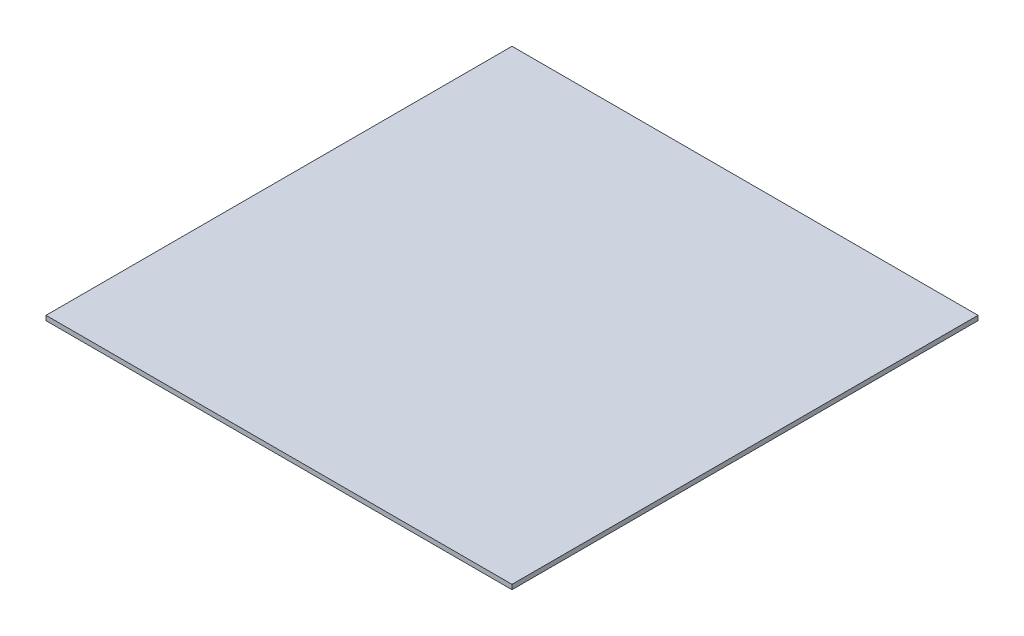
SolidWorks part; units mm, degrees
ref_plane "Płaszczyzna przednia" through (0, 0, 0) normal (0, 0, 1) x (1, 0, 0)
ref_plane "Płaszczyzna górna" through (0, 0, 0) normal (0, 1, 0) x (1, 0, 0)
ref_plane "Płaszczyzna prawa" through (0, 0, 0) normal (1, 0, 0) x (0, 0, -1)
sketch "Szkic1" plane through (0, 0, 0) normal (0, 1, 0) x (1, 0, 0)
  line L1 (-5000, -5000) -> (5000, -5000)
  line L2 (-5000, -5000) -> (-5000, 5000)
  line L3 (-5000, 5000) -> (5000, 5000)
  line L4 (5000, -5000) -> (5000, 5000)
  line L5 (-5000, -5000) -> (5000, 5000) construction
  line L6 (-5000, 5000) -> (5000, -5000) construction
  point P0 (0, 0)
  dimension "D1" = 10000
  dimension "D2" = 10000
extrude "Dodanie-wyciągnięcie1" add sketch "Szkic1" along normal blind 100
